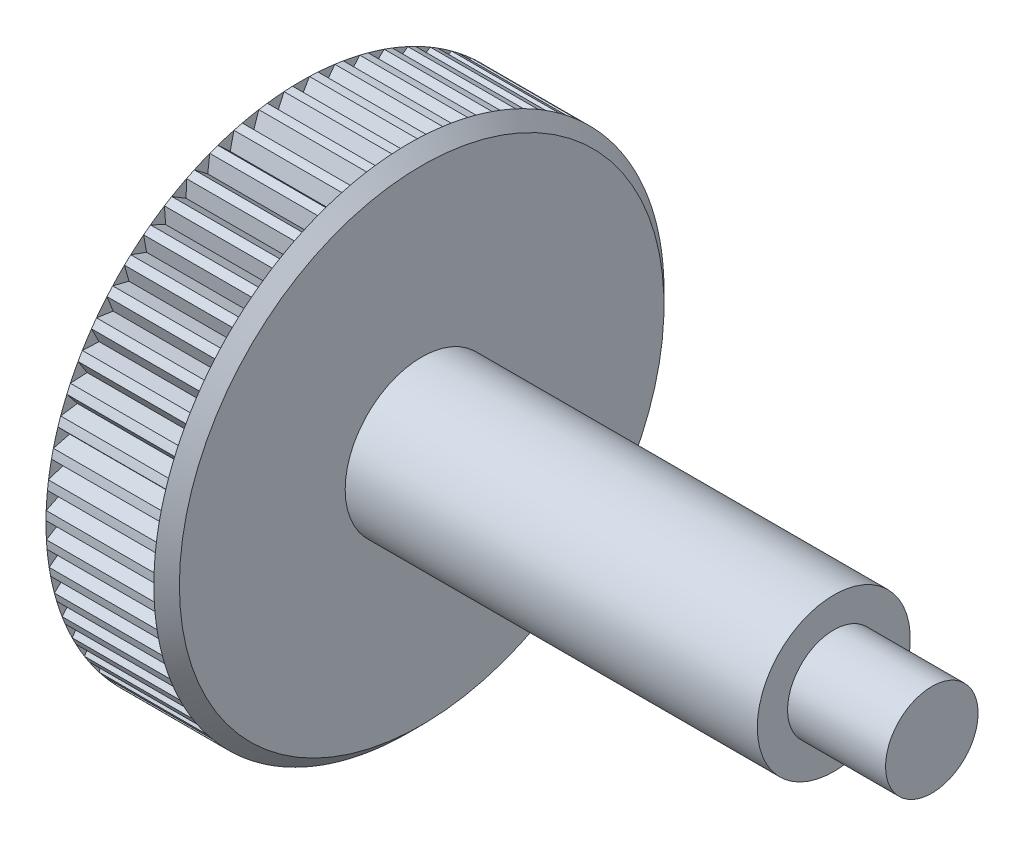
SolidWorks part; units mm, degrees
ref_plane "Front" through (0, 0, 0) normal (0, 0, 1) x (1, 0, 0)
ref_plane "Top" through (0, 0, 0) normal (0, 1, 0) x (1, 0, 0)
ref_plane "Right" through (0, 0, 0) normal (1, 0, 0) x (0, 0, -1)
sketch "Sketch1" plane through (0, 0, 0) normal (0, 0, 1) x (1, 0, 0)
  line L0 (0, 0) -> (26, 0)
  line L1 (1.2702, 10) -> (6, 10)
  line L2 (6, 10) -> (6, 3)
  line L3 (26, 0) -> (26, 1.814)
  line L4 (22.1577, 3) -> (22.1577, 1.814)
  line L5 (22.1577, 1.814) -> (26, 1.814)
  line L7 (6, 3) -> (22.1577, 3)
  line L9 (-48.2111, 0) -> (101.1311, 0) construction
  arc A1 (1.2702, 10) -> (0, 0) centre (40, 0) ccw
  dimension "l" = 20
  dimension "k" = 6
revolve "Base" add sketch "Sketch1" angle 360 about L9
cosmetic thread "ThreadCosmetic1" [suppressed] parameters "THD_MINOR"=4.5
chamfer "Chamfer1" distance 0.5 angle 45 1 edges at (6, 0, 10)
ref_plane "Plane1" through (1.2702, 0, 0) normal (1, 0, 0) x (0, 0, -1)
ref_plane "Plane2" through (5.5, 0, 0) normal (1, 0, 0) x (0, 0, -1)
sketch "Sketch2" plane through (1.2702, 0, 0) normal (1, 0, 0) x (0, 0, -1)
  line L1 (0, 9.4226) -> (0.5, 10.2887)
  line L2 (0.5, 10.2887) -> (-0.5, 10.2887)
  line L3 (-0.5, 10.2887) -> (0, 9.4226)
  circle A0 centre (0, 0) radius 10 construction
  circle A2 centre (0, 10) radius 0.2887 construction
  dimension "D1" = 1
extrude "Cut-Extrude1" cut sketch "Sketch2" along normal up to surface (4.2298 mm away) up to plane "Plane2"
pattern_circular "Circular-Pattern1" count 63 over 360 about axis through (-48.2111, 0, 0) along (1, 0, 0) of "Cut-Extrude1"
sketch "Sketch3" plane through (0, 0, 0) normal (0, 0, 1) x (1, 0, 0)
  line L0 (21.7827, 3.75) -> (22.5327, 3.75)
  line L1 (22.5327, 3.75) -> (22.5327, 3)
  line L2 (22.5327, 3) -> (22.1577, 2.3505)
  line L3 (22.1577, 2.3505) -> (21.7827, 3)
  line L4 (21.7827, 3) -> (21.7827, 3.75)
  line L5 (22.1577, -3) -> (22.1577, 3) construction
  line L6 (22.1577, 3) -> (6, 3) construction
  dimension "D1" = 0.75
revolve "Cut-Revolve10" [suppressed] cut sketch "Sketch3" angle 360 about axis through (-48.2111, 0, 0) along (1, 0, 0)
pattern_linear "LPattern10" [suppressed] count 18 along (-1, 0, 0) of bodies 104
equation "\"D1@Circular-Pattern1\" =int (  \"dk@Sketch1\" * PI+1 ) "
equation "\"D1@Plane2\" = \"c@Chamfer1\""
equation "\"D1@Sketch3\" =  ( \"d@Sketch1\" - \"THD_MINOR@ThreadCosmetic1\" )  / 2"
equation "\"pitch@LPattern10\" = 1.2 * \"D1@Sketch3\""
equation "\"D1@LPattern10\" =  ( \"l@Sketch1\" - \"z@Sketch1\" )  / \"pitch@LPattern10\""
